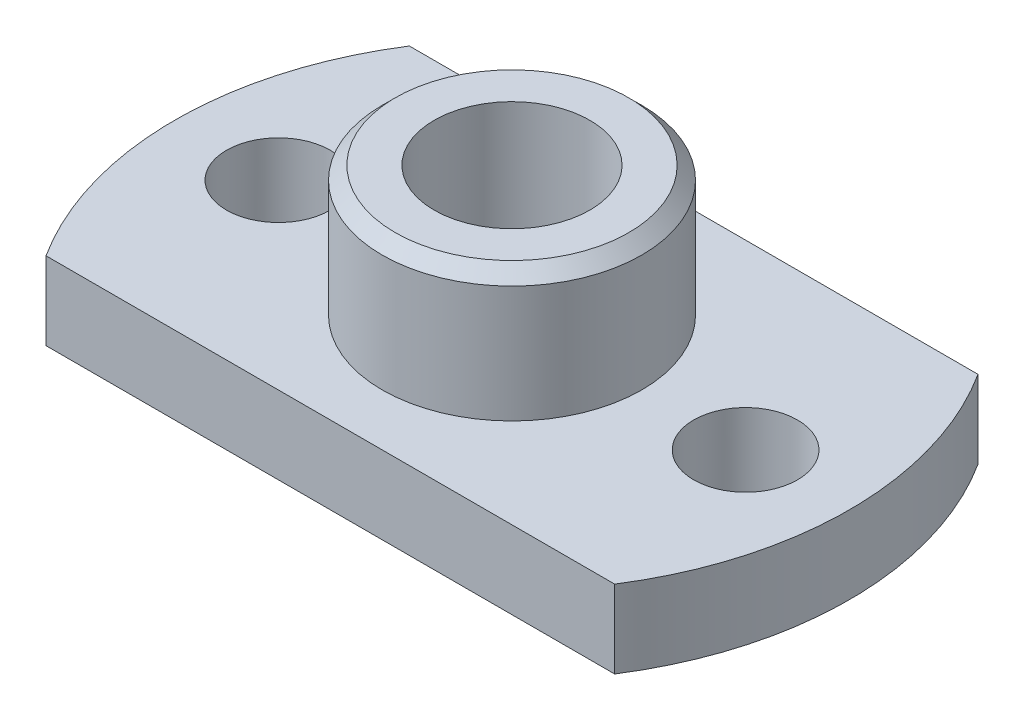
SolidWorks part; units mm, degrees
ref_plane "Front Plane" through (0, 0, 0) normal (0, 0, 1) x (1, 0, 0)
ref_plane "Top Plane" through (0, 0, 0) normal (0, 1, 0) x (1, 0, 0)
ref_plane "Right Plane" through (0, 0, 0) normal (1, 0, 0) x (0, 0, -1)
sketch "Base Sketch" plane through (0, 0, 0) normal (0, 1, 0) x (1, 0, 0)
  line L1 (-5.4772, -3.5) -> (5.4772, -3.5)
  line L2 (-5.4772, -3.5) -> (-5.4772, 3.5)
  line L3 (-5.4772, 3.5) -> (5.4772, 3.5)
  line L4 (5.4772, -3.5) -> (5.4772, 3.5)
  line L5 (-5.4772, -3.5) -> (5.4772, 3.5) construction
  line L6 (-5.4772, 3.5) -> (5.4772, -3.5) construction
  arc A0 (5.4772, 3.5) -> (5.4772, -3.5) centre (0, 0) cw
  arc A1 (-5.4772, -3.5) -> (-5.4772, 3.5) centre (0, 0) cw
  point P0 (0, 0)
  point P8 (-6.5, 0)
  point P9 (6.5, 0)
  dimension "D1" = 6.5
  dimension "D2" = 13
  dimension "D3" = 7
extrude "Base Extrude" add sketch "Base Sketch" along normal blind 1.5 contours L1 L4 L3 L2 | A1 L2 | A0 L4 region at (0, 0, 0) region at (-5.8892, 0, 0) region at (5.8892, 0, 0)
sketch "5mm diameter Sketch" plane through (0, 0, 0) normal (0, 1, 0) x (1, 0, 0)
  circle A0 centre (0, 0) radius 2.5
  dimension "D1" = 5
extrude "Protrusion Extrude" add sketch "5mm diameter Sketch" along normal blind 2.5 from surface starting at face at (0, 1.5, 0)
extrude "5mm Bottom Cut" cut sketch "5mm diameter Sketch<2>" along normal blind 0.7 from surface starting at face at (0, 0, 0)
sketch "5mm diameter Sketch<2>" plane through (0, 0, 0) normal (0, 1, 0) x (1, 0, 0) same geometry as "5mm diameter Sketch"
fillet "Chamfer1" radius 0.25 1 edges at (0, 4, 2.5) type face fillet profile chamfer first side face at (0, 4, 2.5) second side face at (0, 4, 2.5)
sketch "Hole Locations Top Plane" plane through (0, 0, 0) normal (0, 1, 0) x (1, 0, 0)
  point P0 (0, 0)
  point P1 (-4.5, 0)
  point P3 (4.5, 0)
  dimension "D1" = 4.5
  dimension "D2" = 9
hole_wizard "Ø2.0 (2) Diameter Hole1" positions "Sketch4" profile "Sketch5" hole size "Ø2.0" standard "ANSI Metric" end condition through all
sketch "Sketch4" plane through (0, 0, 0) normal (0, -1, 0) x (-1, 0, 0)
  point P0 (4.5, 0)
  point P3 (-4.5, 0)
sketch "Sketch5" plane through (-4.5, 0, 0) normal (1, 0, 0) x (0, 0, -1)
  line L0 (0, 0) -> (0, 4)
  line L1 (0, 4) -> (1, 4)
  line L2 (1, 4) -> (1, 0)
  line L5 (1, 0) -> (0, 0)
  line L11 (0, -6.35) -> (0, 107.95) construction
  dimension "Thru Hole Dia." = 2
  dimension "Thru Hole Depth" = 4
hole_wizard "Ø2.5 (2.5) Diameter Hole1" positions "Sketch6" profile "Sketch7" hole size "Ø2.5" standard "ANSI Metric" end condition through all
sketch "Sketch6" plane through (0, 0.7, 0) normal (0, -1, 0) x (-1, 0, 0)
  point P0 (0, 0)
sketch "Sketch7" plane through (0, 0.7, 0) normal (1, 0, 0) x (0, 0, -1)
  line L0 (0, 0) -> (0, 3.3)
  line L1 (0, 3.3) -> (1.25, 3.3)
  line L2 (1.25, 3.3) -> (1.25, 0)
  line L5 (1.25, 0) -> (0, 0)
  line L11 (0, -6.35) -> (0, 107.95) construction
  dimension "Thru Hole Dia." = 2.5
  dimension "Thru Hole Depth" = 3.3
sketch "3mm Diameter Sketch" plane through (0, 0, 0) normal (0, 1, 0) x (1, 0, 0)
  circle A0 centre (0, 0) radius 1.5
  dimension "D1" = 3
extrude "Cut-Extrude2" cut sketch "3mm Diameter Sketch" against normal up to surface (-1.5 mm away) from surface up to face at (-4.5, 1.5, 1) starting at face at (0, 4, -1.25)
